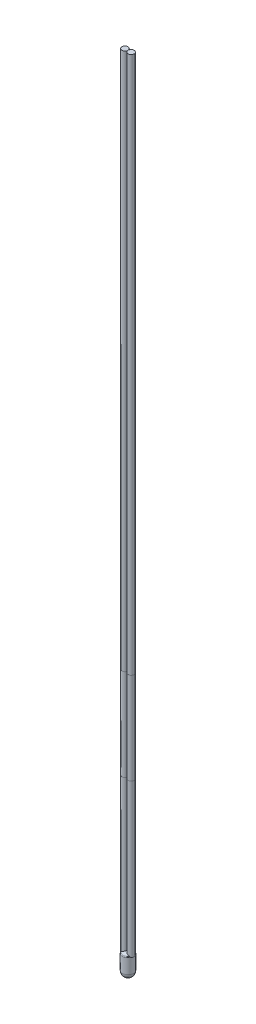
SolidWorks part; units mm, degrees
ref_plane "Alzado" through (0, 0, 0) normal (0, 0, 1) x (1, 0, 0)
ref_plane "Planta" through (0, 0, 0) normal (0, 1, 0) x (1, 0, 0)
ref_plane "Vista lateral" through (0, 0, 0) normal (1, 0, 0) x (0, 0, -1)
sketch "Croquis1" plane through (0, 0, 0) normal (0, 0, 1) x (1, 0, 0)
  line L0 (0, 0) -> (0, 2.5)
  line L1 (0.9, 2.8825) -> (0.9, -0.9)
  line L2 (0.9, 2.8825) -> (0.9, -0.9) construction
  arc A0 (0, 0) -> (0.9, -0.9) centre (0.9, 0) ccw
  arc A2 (0.9, 2.8825) -> (0, 2.5) centre (0.9, 1.6325) ccw
  dimension "D1" = 0.9
  dimension "D4" = 1.25
  dimension "D2" = 3.7825
  dimension "D3" = 1.6325
revolve "Revolución2" add sketch "Croquis1" angle 360 about L2
fillet "Redondeo1" radius 0.2 1 edges at (0, 2.5, 0)
ref_plane "Plano1" through (0, 2.4152, 0) normal (0, -1, 0) x (-1, 0, 0)
sketch "Croquis2" plane through (0, 2.4152, 0) normal (0, -1, 0) x (-1, 0, 0)
  line L0 (0, 0) -> (-2.221, 0) construction
  circle A1 centre (-1.41, 0) radius 0.5
  circle A2 centre (-0.4, 0) radius 0.5
  dimension "D3" = 1.01
  dimension "D1" = 1
  dimension "D2" = 0.4
extrude "Saliente-Extruir1" add sketch "Croquis2" against normal blind 25
sketch3d "Croquis3D3" [suppressed]
  spline S0 degree 3 poles (1.41, 2.4152, 0) (1.0603, 3.5631, 0.3272) (1.6484, 7.3886, 0.0467) (7.5523, 7.6503, -0.6505) (8.4693, 8.1567, 9.8569) (15.0427, 7.9249, 12.7408) (19.1583, 7.6729, 13.628) knots 0 0 0 0 0.164635 0.28119 0.551672 1 1 1 1
  spline S1 degree 3 poles (0.4, 2.4152, 0) (0.4448, 4.6268, 0.3906) (0.6458, 7.7943, -0.1737) (6.3043, 8.4584, -0.8157) (9.3949, 8.4545, 3.1205) (6.9679, 9.5284, 10.8325) (19.295, 8.8861, 13.6236) knots 0 0 0 0 0.158889 0.351328 0.437845 1 1 1 1
sketch "Croquis3" [suppressed] plane through (0, 2.4152, 0) normal (0, -1, 0) x (-1, 0, 0)
  line L0 (-0.9, 0.8333) -> (-0.9, -0.8333) construction
  line L1 (-0.0667, 0) -> (-1.7333, 0) construction
  circle A0 centre (-1.37, 0) radius 0.45
  circle A1 centre (-0.43, 0) radius 0.45
  circle A2 centre (-0.9, 0) radius 0.8333 construction
  dimension "D2" = 0.9
  dimension "D1" = 0.47
ref_plane "Plano2" [suppressed] through (0.43, 0, 0) normal (1, 0, 0) x (0, 0, -1)
sketch "Croquis5" [suppressed] plane through (0.43, 0, 0) normal (1, 0, 0) x (0, 0, -1)
  line L0 (0, 2.4152) -> (0, 3.5168)
sketch "Croquis6" [suppressed] plane through (0, 0, 0) normal (0, 0, 1) x (1, 0, 0)
  line L0 (0.43, 3.5168) -> (8.4601, 14.9849)
  line L1 (0.43, 3.5168) -> (6.2015, 3.5168) construction
  line L2 (8.4601, 14.9849) -> (14.7151, 6.6842) construction
  dimension "D1" = 14
  dimension "D2" = 55
  dimension "D3" = 72
ref_plane "Plano3" [suppressed] through (12.2183, 9.2072, -2.6976) normal (0.7865, 0.5927, -0.1736) x (0.2514, -0.5641, -0.7865)
sketch "Croquis7" [suppressed] plane through (12.2183, 9.2072, -2.6976) normal (0.7865, 0.5927, -0.1736) x (0.2514, -0.5641, -0.7865)
  line L0 (-6.3258, 3.843) -> (-24.1613, -12.2162)
  line L1 (-6.3258, 3.843) -> (-6.3258, 15.4439) construction
  dimension "D1" = 132
  dimension "D2" = 24
ref_plane "Plano4" [suppressed] through (-4.1263, 5.5348, 0.607) normal (0.5954, -0.7986, -0.0876) x (-0.8025, -0.5964, -0.0175)
sketch "Croquis8" [suppressed] plane through (-4.1263, 5.5348, 0.607) normal (0.5954, -0.7986, -0.0876) x (-0.8025, -0.5964, -0.0175)
  line L0 (-20.3032, -22.6735) -> (-23.3032, -22.6735)
  line L1 (-23.3032, -22.6735) -> (-28.501, -47.1272)
  line L2 (-28.501, -47.1272) -> (-62.604, -39.2539)
  line L3 (-62.604, -39.2539) -> (-57.0398, -16.9371)
  dimension "D1" = 102
  dimension "D2" = 3
  dimension "D3" = 25
  dimension "D4" = 89
  dimension "D5" = 89
  dimension "D6" = 23
  dimension "D7" = 35
ref_plane "Plano5" [suppressed] through (42.2967, 38.1848, 18.4753) normal (-0.2313, -0.066, -0.9707) x (-0.9728, 0.0053, 0.2314)
sketch "Croquis9" [suppressed] plane through (42.2967, 38.1848, 18.4753) normal (-0.2313, -0.066, -0.9707) x (-0.9728, 0.0053, 0.2314)
  line L0 (0, 0) -> (-2.2943, -3.2766)
  line L1 (0, 0) -> (0, 5.9543) construction
  line L2 (0, 0) -> (7.2144, 0) construction
  dimension "D1" = 145
  dimension "D2" = 4
sketch3d "Croquis3D4" [suppressed]
  line L0 (0.43, 2.4152, 0) -> (0.43, 3.5168, 0) construction
  line L1 (0.43, 3.5168, 0) -> (8.4601, 14.9849, 0) construction
  line L2 (8.4601, 14.9849, 0) -> (13.0346, 15.8129, 23.5454) construction
  line L3 (13.0346, 15.8129, 23.5454) -> (15.4421, 17.602, 23.598) construction
  line L4 (15.4421, 17.602, 23.598) -> (20.5489, 18.728, 48.0449) construction
  line L5 (20.5489, 18.728, 48.0449) -> (47.6158, 39.7017, 40.8003) construction
  line L6 (47.6158, 39.7017, 40.8003) -> (42.2967, 38.1848, 18.4753) construction
  line L7 (0.43, 2.4152, 0) -> (0.43, 2.8862, 0)
  line L8 (0.7917, 4.0333, 0) -> (4.4648, 9.2791, 0)
  line L9 (9.7877, 15.2252, 6.8336) -> (12.7989, 15.7703, 22.3322)
  line L10 (14.027, 16.5504, 23.5671) -> (14.4673, 16.8776, 23.5767)
  line L11 (15.6903, 17.6567, 24.7858) -> (19.3017, 18.453, 42.0744)
  line L12 (25.2706, 22.3868, 46.7811) -> (41.3201, 34.8233, 42.4854)
  line L13 (45.7331, 39.1648, 32.8984) -> (42.7593, 38.3167, 20.4166)
  line L14 (42.2967, 38.1848, 18.4753) -> (44.562, 34.9033, 18.1586) construction
  line L15 (43.4294, 36.544, 18.3169) -> (44.562, 34.9033, 18.1586)
  arc A0 (41.3201, 34.8233, 42.4854) -> (45.7331, 39.1648, 32.8984) centre (39.5777, 34.3793, 34.6901) ccw
  arc A1 (4.4648, 9.2791, 0) -> (9.7877, 15.2252, 6.8336) centre (5.3669, 8.6474, 7.9238) ccw
  arc A2 (19.3017, 18.453, 42.0744) -> (25.2706, 22.3868, 46.7811) centre (23.9638, 22.0537, 40.9347) ccw
  arc A3 (14.4673, 16.8776, 23.5767) -> (15.6903, 17.6567, 24.7858) centre (14.5247, 16.7566, 25.0707) ccw
  arc A4 (12.7989, 15.7703, 22.3322) -> (14.027, 16.5504, 23.5671) centre (13.9696, 16.6715, 22.0731) ccw
  arc A5 (42.7593, 38.3167, 20.4166) -> (43.4294, 36.544, 18.3169) centre (43.8919, 36.6759, 20.2582) ccw
  arc A6 (0.43, 2.8862, 0) -> (0.7917, 4.0333, 0) centre (2.43, 2.8862, 0) ccw
  point P11 (47.6158, 39.7017, 40.8003)
  point P13 (34.8145, 40.7684, 35.3908)
  point P16 (8.4601, 14.9849, 0)
  point P18 (11.8577, 4.1025, 6.8226)
  point P21 (20.5489, 18.728, 48.0449)
  point P23 (20.3914, 26.8456, 41.4602)
  point P26 (15.4421, 17.602, 23.598)
  point P28 (15.4178, 15.5586, 24.9393)
  point P31 (13.0346, 15.8129, 23.5454)
  point P33 (13.0765, 17.8694, 22.2045)
  point P36 (42.2967, 38.1848, 18.4753)
  point P38 (42.3098, 35.5399, 20.7124)
  point P41 (0.43, 3.5168, 0)
  point P43 (2.43, 2.8862, -2)
  dimension "D1" = 8
  dimension "D2" = 6
  dimension "D3" = 1.5
  dimension "D4" = 2
  dimension "D5" = 2
sweep "Barrer1" [suppressed] add profiles "Croquis3" path "Croquis3D4"
extrude "Saliente-Extruir6" add sketch "Croquis2<3>" against normal blind 15 from offset 25 separate body offset against normal yes
sketch "Croquis2<3>" plane through (0, 2.4152, 0) normal (0, -1, 0) x (-1, 0, 0) same geometry as "Croquis2"
extrude "Saliente-Extruir7" add sketch "Croquis2<4>" against normal blind 88 from offset 40 separate body offset against normal yes
sketch "Croquis2<4>" plane through (0, 2.4152, 0) normal (0, -1, 0) x (-1, 0, 0) same geometry as "Croquis2"
